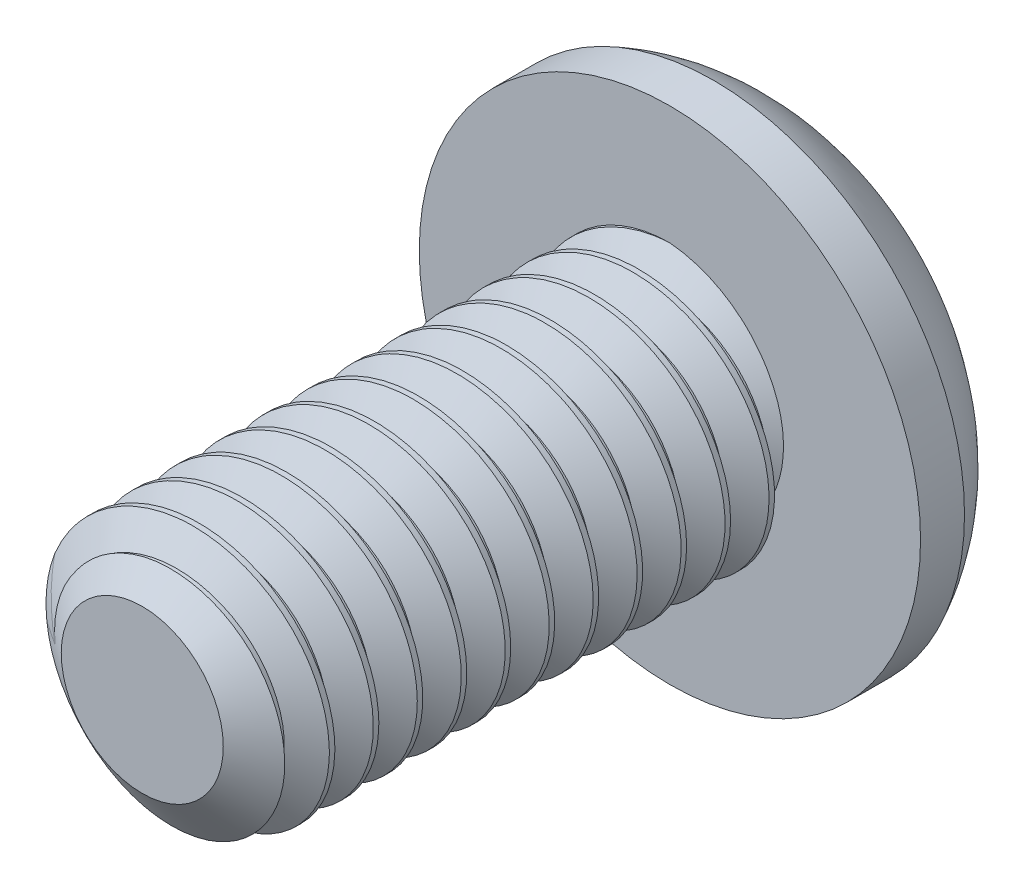
SolidWorks part; units mm, degrees
ref_plane "Front Plane" through (0, 0, 0) normal (0, 0, 1) x (1, 0, 0)
ref_plane "Top Plane" through (0, 0, 0) normal (0, 1, 0) x (1, 0, 0)
ref_plane "Right Plane" through (0, 0, 0) normal (1, 0, 0) x (0, 0, -1)
sketch "Sketch1" plane through (0, 0, 0) normal (0, 0, 1) x (1, 0, 0)
  circle A0 centre (0, 0) radius 1.5
  dimension "OD" = 3
extrude "Extrude1" add sketch "Sketch1" against normal blind 6
sketch "Sketch2" plane through (0, 0, 0) normal (0, 0, 1) x (1, 0, 0)
  circle A0 centre (0, 0) radius 1.5 construction
  circle A1 centre (0, 0) radius 1.5
curve "Helix/Spiral1" pitch 0.5 height 6.5 radius 1.5 centre (0, 0, 0) axis (0, 0, -1) start towards (0, 1, 0) parameters "pitch"=0.5
sketch "Sketch3" plane through (0, 0, 0) normal (1, 0, 0) x (0, 0, -1)
  line L0 (-0.4375, 1.5) -> (-0.25, 1.1752)
  line L1 (-0.25, 1.1752) -> (-0.1875, 1.1752)
  line L2 (-0.1875, 1.1752) -> (0, 1.5)
  line L3 (-0.4375, 1.5) -> (0, 1.5)
  line L4 (-0.2187, 1.5) -> (-0.2187, 1.1752) construction
  line L5 (-0.3437, 1.3376) -> (-0.0937, 1.3376) construction
  line L6 (0, 1.5) -> (0, -1.5) construction
  dimension "D1" = 0.0625
  dimension "D2" = 0.25
  dimension "D3" = 60
sweep "Cut-Sweep1" cut profiles "Sketch3" path "Helix/Spiral1"
sketch "Sketch4" plane through (0, 0, 0) normal (1, 0, 0) x (0, 0, -1)
  line L0 (0.4053, 1.5) -> (0, 0.9212)
  line L1 (0, 0.9212) -> (0, 1.5)
  line L2 (0.4053, 1.5) -> (0, 1.5)
  line L3 (-0.4375, 1.5) -> (0, 1.5) construction
  line L4 (0, 0) -> (7.0209, 0) construction
  dimension "D1" = 55
  dimension "D2" = 0.254
revolve "Cut-Revolve1" cut sketch "Sketch4" angle 360 about L4
sketch "Sketch5" plane through (0, 0, 0) normal (1, 0, 0) x (0, 0, -1)
  line L0 (6, -1.1822) -> (6, 1.0703) construction
  line L1 (6, 1.627) -> (28.1202, 1.627)
  line L2 (6, 1.627) -> (6, 0)
  line L3 (6, 0) -> (28, 0)
  line L4 (28, 1.2968) -> (28, 0)
  line L5 (28.1202, 1.627) -> (28, 1.2968)
  line L6 (0, 0) -> (9.9695, 0) construction
  point P3 (28, 1.627)
  point P10 (28, 1.627)
  dimension "D1" = 0.3302
  dimension "Thread min" = 28
  dimension "D2" = 0.127
  dimension "D3" = 20
revolve "partially thread" [suppressed] add sketch "Sketch5" angle 360 about L6
sketch "Sketch6" plane through (0, 0, -6) normal (0, 0, -1) x (-1, 0, 0)
  circle A0 centre (0, 0) radius 2.85
  dimension "head dia" = 5.7
extrude "Extrude2" add sketch "Sketch6" along normal blind 1.65
sketch "Sketch10" plane through (0, 0, 0) normal (1, 0, 0) x (0, 0, -1)
  line L0 (7.65, -2.85) -> (7.65, 2.85) construction
  line L1 (0, 0) -> (15.9584, 0) construction
  line L2 (7.65, 2.85) -> (6, 2.85) construction
  line L3 (6, 2.85) -> (6, -2.85) construction
  line L4 (6.5, 2.85) -> (6.5, 3.35)
  line L5 (6.5, 3.35) -> (8.15, 3.35)
  line L6 (8.15, 3.35) -> (8.15, 1)
  line L7 (7.65, 1) -> (8.15, 1)
  arc A0 (7.65, 1) -> (6.5, 2.85) centre (5.587, 1) ccw
  dimension "D1" = 2
  dimension "D2" = 0.5
  dimension "D3" = 0.5
revolve "Cut-Revolve2" cut sketch "Sketch10" angle 360 about L1
ref_plane "Plane1" through (0, 0, -7.65) normal (0, 0, 1) x (1, 0, 0)
sketch "Sketch7" plane through (0, 0, -7.65) normal (0, 0, -1) x (-1, 0, 0)
  line L1 (0, 1.1547) -> (-1, 0.5774)
  line L2 (-1, 0.5774) -> (-1, -0.5774)
  line L3 (-1, -0.5774) -> (0, -1.1547)
  line L4 (0, -1.1547) -> (1, -0.5774)
  line L5 (1, -0.5774) -> (1, 0.5774)
  line L6 (1, 0.5774) -> (0, 1.1547)
  circle A0 centre (0, 0) radius 1 construction
  dimension "hex dia" = 2
extrude "Cut-Extrude1" cut sketch "Sketch7" against normal blind 1.5
sketch "Sketch8" plane through (0, 0, -7.65) normal (0, 0, 1) x (1, 0, 0)
  circle A0 centre (0, 0) radius 1.1547
extrude "Cut-Extrude2" cut sketch "Sketch8" along normal through all draft 45
sketch "Sketch9" plane through (0, 0, 0) normal (1, 0, 0) x (0, 0, -1)
  line L0 (0, 1.5) -> (0, -1.5) construction
  line L1 (2.75, 1.5) -> (2.75, -1.5) construction
  dimension "D1" = 2.75
  dimension "D4" = 0.635
  dimension "D5" = 0.3302
equation "\"D3@Helix/Spiral1\" = \"screw length@Extrude1\"+\"pitch@Helix/Spiral1\""
equation "\"D1@Sketch3\" = \"pitch@Helix/Spiral1\"*.125"
equation "\"D2@Sketch3\" = \"pitch@Helix/Spiral1\"*.5"
equation "\"D1@Cut-Extrude1\" = \"hex dia@Sketch7\"*.75"
equation "\"D1@Sketch9\" = \"pitch@Helix/Spiral1\"*5.5"
equation "\"D1@Sketch10\" = \"hex dia@Sketch7\""
equation "\"D1@Plane1\" = \"head depth@Extrude2\""
